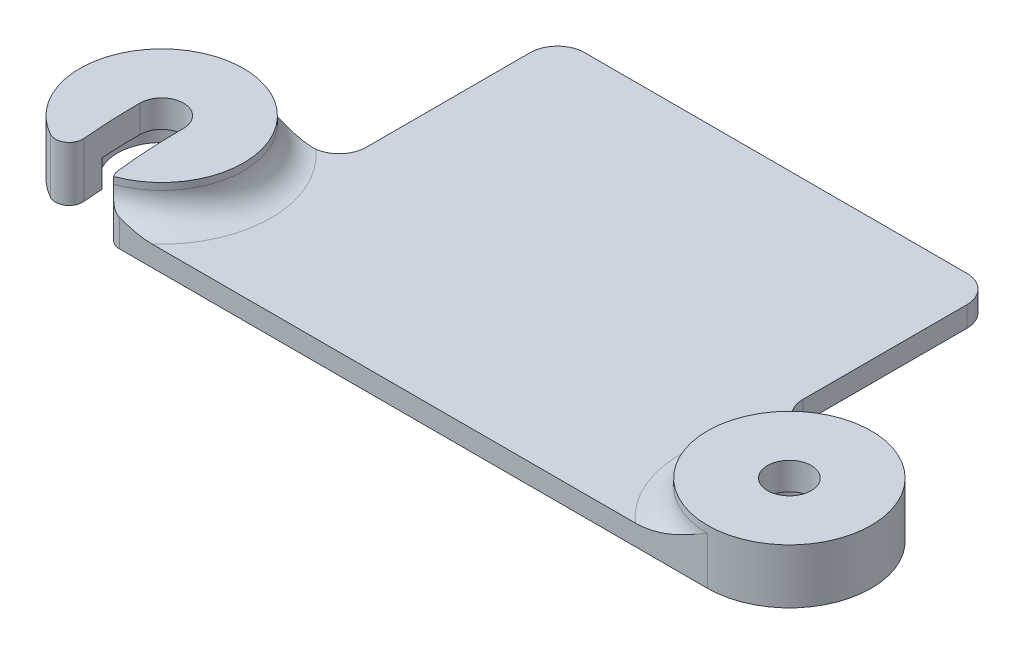
SolidWorks part; units mm, degrees
material "ABS"
ref_plane "Plan de face" through (0, 0, 0) normal (0, 0, 1) x (1, 0, 0)
ref_plane "Plan de dessus" through (0, 0, 0) normal (0, 1, 0) x (1, 0, 0)
ref_plane "Plan de droite" through (0, 0, 0) normal (1, 0, 0) x (0, 0, -1)
sketch "Esquisse1" plane through (0, 0, 0) normal (0, 1, 0) x (1, 0, 0)
  line L1 (-16, 28) -> (16, 28)
  line L2 (-16, 28) -> (-16, 0)
  line L3 (-16, 0) -> (16, 0)
  line L4 (16, 28) -> (16, 0)
  dimension "D1" = 28
  dimension "D2" = 32
extrude "Boss.-Extru.1" add sketch "Esquisse1" along normal blind 1.5
sketch "Esquisse2" plane through (0, 0, 0) normal (0, 1, 0) x (1, 0, 0)
  line L0 (-23, 6) -> (23, 6) construction
  line L1 (-23, 12) -> (23, 12)
  line L2 (-23, 0) -> (23, 0)
  arc A0 (-23, 12) -> (-23, 0) centre (-23, 6) ccw
  arc A1 (23, 0) -> (23, 12) centre (23, 6) ccw
  point P2 (0, 6)
  point P7 (0, 0)
  dimension "D2" = 6
  dimension "D1" = 46
extrude "Boss.-Extru.2" add sketch "Esquisse2" along normal up to surface (1.5 mm away) up to face at (0, 1.5, -14)
sketch "Esquisse3" plane through (0, 0, 0) normal (0, 1, 0) x (1, 0, 0)
  circle A0 centre (-23, 6) radius 6
  circle A1 centre (23, 6) radius 6
  arc A2 (23, 0) -> (23, 12) centre (23, 6) ccw construction
  arc A3 (-23, 12) -> (-23, 0) centre (-23, 6) ccw construction
extrude "Boss.-Extru.3" add sketch "Esquisse3" along normal blind 4
fillet "Congé2" radius 2 2 edges at (-16, 0.75, -12) (16, 0.75, -12)
fillet "Congé1" radius 2 4 edges at (-16, 0.75, -28) (16, 0.75, -28) (17, 1.5, -6) (-17, 1.5, -6)
hole_wizard "Chambrage pour vis à tête cylindrique à 6 pans creux (ou vis CHC) M31" positions "Esquisse5" profile "Esquisse4" counterbore size "M3" standard "Ansi Metric" end condition through all
sketch "Esquisse5" plane through (0, 0, 0) normal (0, -1, 0) x (-1, 0, 0)
  arc A0 (-23, 12) -> (-23, 0) centre (-23, 6) ccw construction
  arc A1 (23, 0) -> (23, 12) centre (23, 6) ccw construction
  point P0 (23, 6)
  point P2 (-23, 6)
sketch "Esquisse4" plane through (-23, 0, -6) normal (1, 0, 0) x (0, 0, -1)
  line L0 (0, 0) -> (0, 4.088)
  line L1 (0, 4.088) -> (1.6, 4.088)
  line L3 (1.6, 4.088) -> (1.6, 2)
  line L4 (1.6, 2) -> (3.25, 2)
  line L5 (3.25, 2) -> (3.25, 0)
  line L7 (3.25, 0) -> (0, 0)
  line L11 (0, -6.35) -> (0, 107.95) construction
  dimension "Diamètre du perçage jusqu'au prochain" = 3.2
  dimension "Profondeur du perçage jusqu'au prochain" = 4.088
  dimension "Diamètre du chambrage" = 6.5
  dimension "Profondeur du chambrage" = 2
sketch "Esquisse6" plane through (0, 4, 0) normal (0, 1, 0) x (1, 0, 0)
  line L0 (-17.7085, 0) -> (17.7085, 0) construction
  line L5 (0, 0) -> (0, 28) construction
  line L6 (14, 28) -> (-14, 28) construction
  arc A1 (-23, 6) -> (-22.5781, -0.2162) centre (23, 6) ccw construction
  arc A2 (-24.6, 6) -> (-24.1634, -0.4324) centre (23, 6) ccw
  arc A3 (-21.4, 6) -> (-20.9927, 0) centre (23, 6) ccw
  arc A4 (-21.4, 6) -> (-24.6, 6) centre (-23, 6) ccw
  arc A5 (-24.1634, -0.4324) -> (-20.9927, 0) centre (-22.5781, -0.2162) ccw
  circle A6 centre (-23, 6) radius 1.6 construction
  point P3 (-22.8944, 2.8847)
extrude "Enlèv. mat.-Extru.2" cut sketch "Esquisse6" against normal through all
fillet "Congé3" radius 1 2 edges at (-24.2365, 2, -0.1288) (-20.9927, 1.2021, 0)
